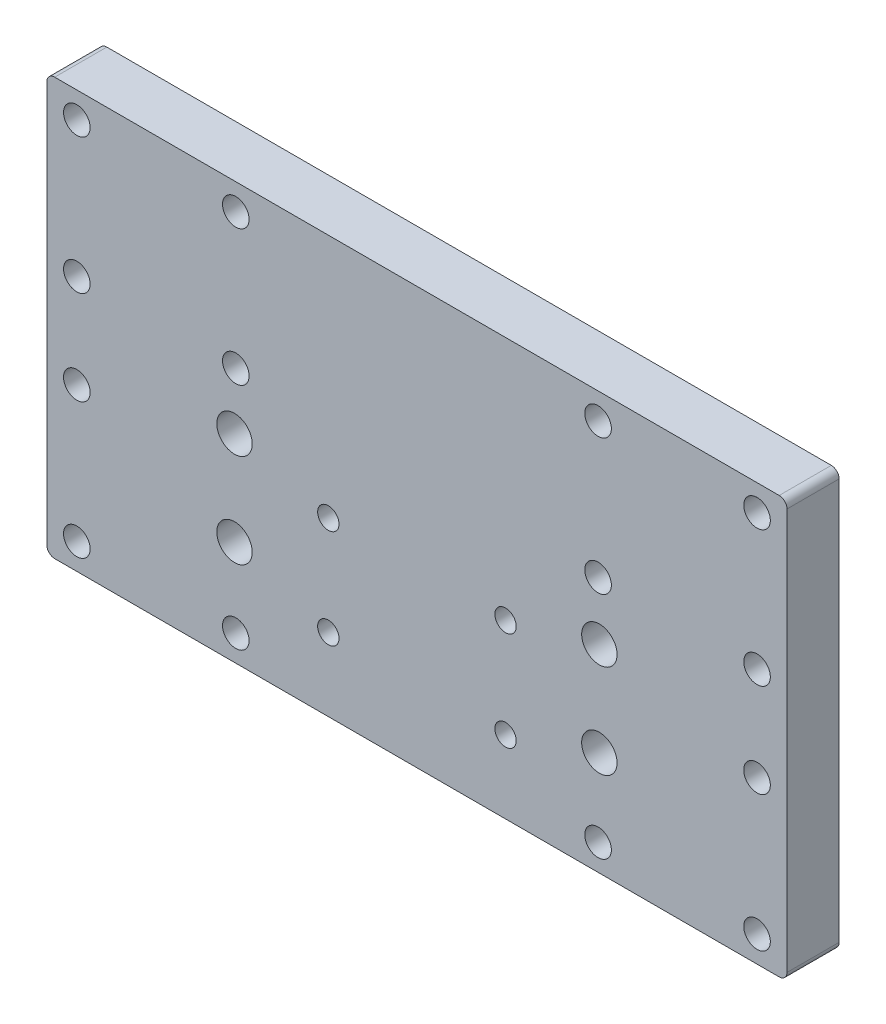
SolidWorks part; units mm, degrees
ref_plane "Front Plane" through (0, 0, 0) normal (0, 0, 1) x (1, 0, 0)
ref_plane "Top Plane" through (0, 0, 0) normal (0, 1, 0) x (1, 0, 0)
ref_plane "Right Plane" through (0, 0, 0) normal (1, 0, 0) x (0, 0, -1)
sketch "Sketch1" plane through (0, 0, 0) normal (0, 0, 1) x (1, 0, 0)
  line L1 (-71, -40) -> (71, -40)
  line L2 (-71, -40) -> (-71, 40)
  line L3 (-71, 40) -> (71, 40)
  line L4 (71, -40) -> (71, 40)
  line L5 (-71, -40) -> (71, 40) construction
  line L6 (-71, 40) -> (71, -40) construction
  point P0 (0, 0)
  dimension "D1" = 80
  dimension "D2" = 142
extrude "Boss-Extrude1" add sketch "Sketch1" along normal mid plane 10
sketch "Sketch2" plane through (0, 0, 5) normal (0, 0, 1) x (1, 0, 0)
  line L3 (-65.25, 40) -> (-65.25, -40)
  line L4 (-65.25, 40) -> (-65.25, -40) construction
  line L6 (65.25, -40) -> (65.25, 40)
  line L7 (65.25, -40) -> (65.25, 40) construction
  line L13 (-34.75, 40) -> (-34.75, -40)
  line L14 (-34.75, 40) -> (-34.75, -40) construction
  line L16 (34.75, -40) -> (34.75, 40)
  line L18 (34.75, -40) -> (34.75, 40) construction
  line L20 (71, 35) -> (-71, 35)
  line L21 (71, 35) -> (-71, 35) construction
  line L23 (-71, -35) -> (71, -35)
  line L24 (-71, -35) -> (71, -35) construction
  line L26 (71, 9) -> (-71, 9)
  line L27 (71, 9) -> (-71, 9) construction
  line L29 (-71, -9) -> (71, -9)
  line L30 (-71, -9) -> (71, -9) construction
  circle A0 centre (-65.25, 35) radius 2.55
  circle A1 centre (-34.75, 35) radius 2.55
  circle A2 centre (-34.75, 9) radius 2.55
  circle A3 centre (-65.25, 9) radius 2.55
  circle A4 centre (65.25, 35) radius 2.55
  circle A5 centre (65.25, 9) radius 2.55
  circle A6 centre (34.75, 9) radius 2.55
  circle A7 centre (34.75, 35) radius 2.55
  circle A8 centre (-65.25, -9) radius 2.55
  circle A10 centre (-34.75, -35) radius 2.55
  circle A11 centre (-65.25, -35) radius 2.55
  circle A13 centre (65.25, -9) radius 2.55
  circle A14 centre (65.25, -35) radius 2.55
  circle A15 centre (34.75, -35) radius 2.55
  dimension "D9" = 5.1
  dimension "D10" = 5.1
  dimension "D11" = 5.1
  dimension "D12" = 5.1
  dimension "D13" = 5.1
  dimension "D14" = 5.1
  dimension "D15" = 5.1
  dimension "D16" = 5.1
  dimension "D17" = 5.1
  dimension "D18" = 5.1
  dimension "D20" = 5.1
  dimension "D21" = 5.1
  dimension "D23" = 5.1
  dimension "D24" = 5.1
  dimension "D1" = 5.75
  dimension "D2" = 5.75
  dimension "D3" = 36.25
  dimension "D4" = 36.25
  dimension "D5" = 5
  dimension "D6" = 5
  dimension "D7" = 31
  dimension "D8" = 31
extrude "Cut-Extrude1" cut sketch "Sketch2" against normal through all
sketch "Sketch3" plane through (0, 0, 5) normal (0, 0, 1) x (1, 0, 0)
  line L0 (-71, -40) -> (71, -40) construction
  line L1 (-17, -7) -> (17, -7) construction
  line L2 (-17, -7) -> (-17, -26) construction
  line L3 (-17, -26) -> (17, -26) construction
  line L4 (17, -7) -> (17, -26) construction
  line L5 (-17, -7) -> (17, -26) construction
  line L6 (-17, -26) -> (17, -7) construction
  line L7 (0, 40) -> (0, -40) construction
  line L8 (71, 40) -> (-71, 40) construction
  circle A0 centre (-17, -7) radius 2.05
  circle A1 centre (-17, -26) radius 2.05
  circle A2 centre (17, -26) radius 2.05
  circle A3 centre (17, -7) radius 2.05
  point P0 (0, 0)
  dimension "D3" = 4.1
  dimension "D4" = 4.1
  dimension "D5" = 4.1
  dimension "D6" = 4.1
  dimension "D1" = 34
  dimension "D2" = 19
  dimension "D7" = 14
  dimension "D8" = 17
extrude "Cut-Extrude2" cut sketch "Sketch3" against normal through all
sketch "Sketch4" plane through (0, 0, 5) normal (0, 0, 1) x (1, 0, 0)
  line L0 (0, 40) -> (0, -40) construction
  line L1 (-35, -20) -> (35, -20) construction
  line L2 (-35, -20) -> (-35, -2) construction
  line L3 (-35, -2) -> (35, -2) construction
  line L4 (35, -20) -> (35, -2) construction
  line L5 (-35, -20) -> (35, -2) construction
  line L6 (-35, -2) -> (35, -20) construction
  line L7 (71, 40) -> (-71, 40) construction
  line L8 (-71, -40) -> (71, -40) construction
  circle A0 centre (-35, -2) radius 3.4
  circle A1 centre (35, -2) radius 3.4
  circle A2 centre (35, -20) radius 3.4
  circle A3 centre (-35, -20) radius 3.4
  point P0 (0, -11)
  dimension "D3" = 6.8
  dimension "D4" = 6.8
  dimension "D5" = 6.8
  dimension "D6" = 6.8
  dimension "D1" = 70
  dimension "D2" = 18
  dimension "D7" = 20
extrude "Cut-Extrude3" cut sketch "Sketch4" against normal through all
fillet "Fillet1" radius 1.5 4 edges at (-71, -40, 0) (71, -40, 0) (71, 40, 0) (-71, 40, 0)
equation "\"D4@Sketch3\"=\"D3@Sketch3\""
equation "\"D5@Sketch3\"=\"D3@Sketch3\""
equation "\"D6@Sketch3\"=\"D3@Sketch3\""
equation "\"D4@Sketch4\"=\"D3@Sketch4\""
equation "\"D5@Sketch4\"=\"D3@Sketch4\""
equation "\"D6@Sketch4\"=\"D3@Sketch4\""
equation "\"D10@Sketch2\"=\"D24@Sketch2\""
equation "\"D16@Sketch2\"=\"D24@Sketch2\""
